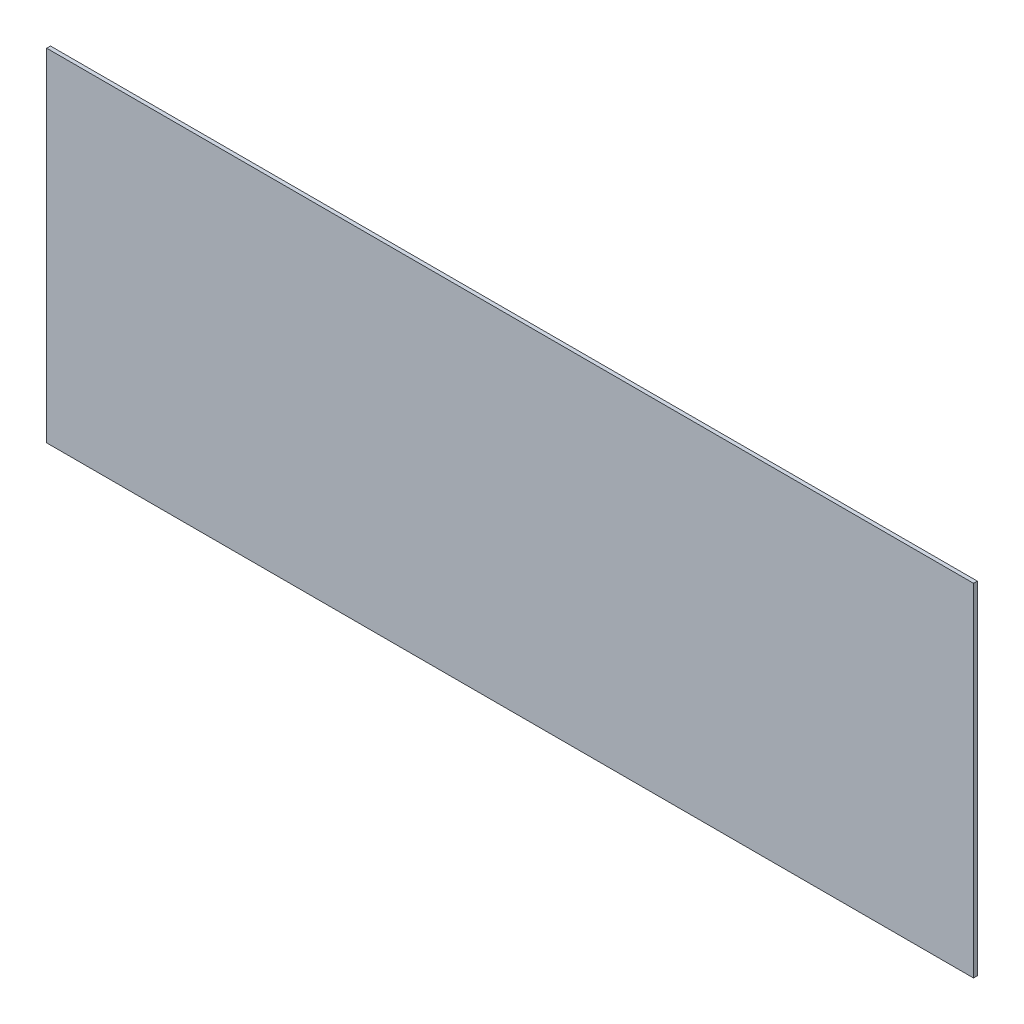
SolidWorks part; units mm, degrees
material "Бальса"
ref_plane "Спереди" through (0, 0, 0) normal (0, 0, 1) x (1, 0, 0)
ref_plane "Сверху" through (0, 0, 0) normal (0, 1, 0) x (1, 0, 0)
ref_plane "Справа" through (0, 0, 0) normal (1, 0, 0) x (0, 0, -1)
sketch "Эскиз1" plane through (0, 0, 0) normal (0, 0, 1) x (1, 0, 0)
  line L1 (0, 0) -> (2440, 0)
  line L2 (0, 0) -> (0, 900)
  line L3 (0, 900) -> (2440, 900)
  line L4 (2440, 0) -> (2440, 900)
  line L8 (2440, 950) -> (2440, 900) construction
  line L9 (0, 950) -> (2440, 950) construction
  line L10 (2440, 950) -> (2440, 900) construction
  dimension "D2" = 900
extrude "Бобышка-Вытянуть1" add sketch "Эскиз1" along normal blind 10
